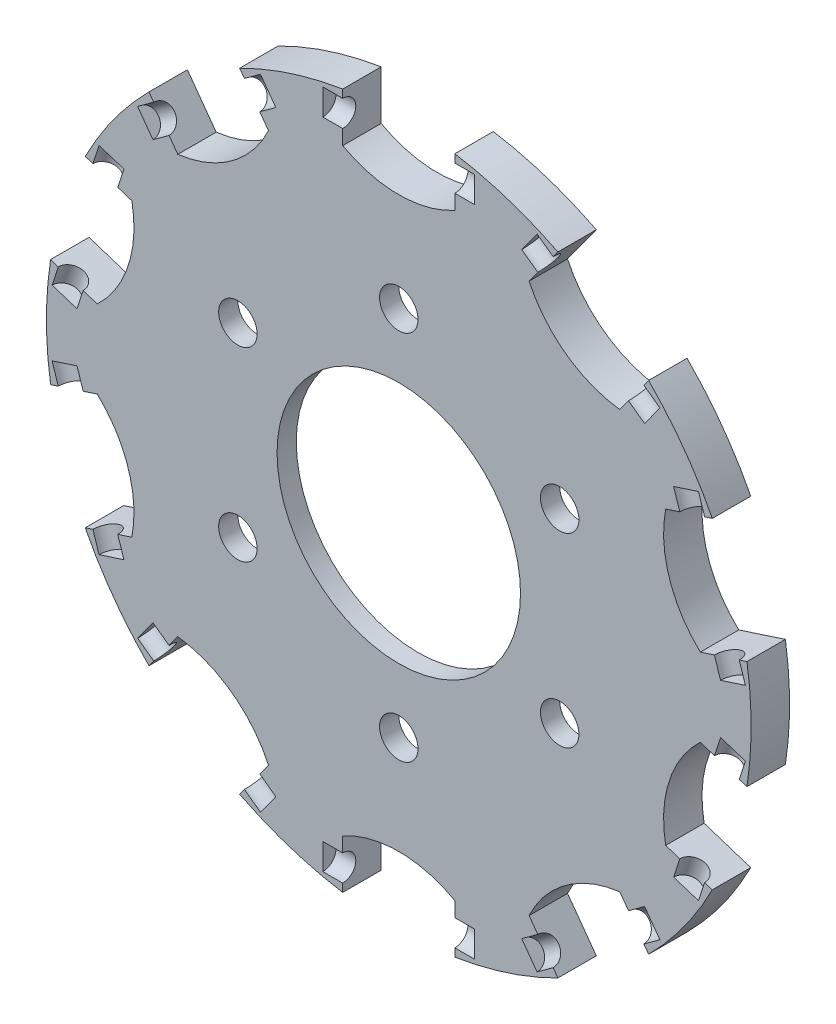
SolidWorks part; units mm, degrees
ref_plane "Front Plane" through (0, 0, 0) normal (0, 0, 1) x (1, 0, 0)
ref_plane "Top Plane" through (0, 0, 0) normal (0, 1, 0) x (1, 0, 0)
ref_plane "Right Plane" through (0, 0, 0) normal (1, 0, 0) x (0, 0, -1)
sketch "Sketch2" plane through (0, 0, 0) normal (0, 0, 1) x (1, 0, 0)
  line L2 (-4.375, 27.1498) -> (-4.375, 23.324)
  line L3 (4.375, 27.1498) -> (4.375, 23.324)
  line L4 (19.4977, 19.3931) -> (17.249, 16.298)
  line L5 (12.4188, 24.5362) -> (10.1701, 21.4411)
  line L6 (27.1729, 4.2289) -> (23.5344, 3.0466)
  line L7 (24.469, 12.5506) -> (20.8305, 11.3684)
  line L8 (24.469, -12.5506) -> (20.8305, -11.3684)
  line L9 (27.1729, -4.2289) -> (23.5344, -3.0466)
  line L10 (12.4188, -24.5362) -> (10.1701, -21.4411)
  line L11 (19.4977, -19.3931) -> (17.249, -16.298)
  line L12 (-4.375, -27.1498) -> (-4.375, -23.324)
  line L13 (4.375, -27.1498) -> (4.375, -23.324)
  line L14 (-19.4977, -19.3931) -> (-17.249, -16.298)
  line L15 (-12.4188, -24.5362) -> (-10.1701, -21.4411)
  line L16 (-27.1729, -4.2289) -> (-23.5344, -3.0466)
  line L17 (-24.469, -12.5506) -> (-20.8305, -11.3684)
  line L18 (-24.469, 12.5506) -> (-20.8305, 11.3684)
  line L19 (-27.1729, 4.2289) -> (-23.5344, 3.0466)
  line L20 (-12.4188, 24.5362) -> (-10.1701, 21.4411)
  line L21 (-19.4977, 19.3931) -> (-17.249, 16.298)
  circle A0 centre (0, 0) radius 27.5
  circle A1 centre (0, 0) radius 14.5 construction
  circle A2 centre (0, 0) radius 18.75 construction
  circle A3 centre (-12.5574, 7.25) radius 1.5
  circle A4 centre (0, 14.5) radius 1.5
  circle A5 centre (12.5574, 7.25) radius 1.5
  circle A6 centre (12.5574, -7.25) radius 1.5
  circle A7 centre (0, -14.5) radius 1.5
  circle A8 centre (-12.5574, -7.25) radius 1.5
  arc A9 (-4.375, 23.324) -> (4.375, 23.324) centre (0, 31.2162) ccw
  arc A10 (10.1701, 21.4411) -> (17.249, 16.298) centre (18.3484, 25.2544) ccw
  arc A11 (20.8305, 11.3684) -> (23.5344, 3.0466) centre (29.6883, 9.6463) ccw
  arc A12 (23.5344, -3.0466) -> (20.8305, -11.3684) centre (29.6883, -9.6463) ccw
  arc A13 (17.249, -16.298) -> (10.1701, -21.4411) centre (18.3484, -25.2544) ccw
  arc A14 (4.375, -23.324) -> (-4.375, -23.324) centre (0, -31.2162) ccw
  arc A15 (-10.1701, -21.4411) -> (-17.249, -16.298) centre (-18.3484, -25.2544) ccw
  arc A16 (-20.8305, -11.3684) -> (-23.5344, -3.0466) centre (-29.6883, -9.6463) ccw
  arc A17 (-23.5344, 3.0466) -> (-20.8305, 11.3684) centre (-29.6883, 9.6463) ccw
  arc A18 (-17.249, 16.298) -> (-10.1701, 21.4411) centre (-18.3484, 25.2544) ccw
  circle A19 centre (0, 0) radius 9.5
  circle A20 centre (0, 0) radius 18.75
  point P25 (0, 0)
  point P75 (0, 0)
  dimension "D1" = 55
  dimension "37" = 29
  dimension "D3" = 37.5
  dimension "D4" = 3
  dimension "D8" = 19
  dimension "D6" = 10
  dimension "D7" = 8.75
  dimension "D5" = 6
extrude "Boss-Extrude2" add sketch "Sketch2" along normal blind 3 contours A18 L21 A0 L18 A17 L19 L16 A16 L17 L14 A15 L15 L12 A14 L13 L10 A13 L11 L8 A12 L9 L6 A11 L7 L4 A10 L5 L3 A9 L2 L20 A8 A1 A3 A4 A5 A6 | A8 A1 A7 A6 A5 A4 A3 A19 region at (-5.1479, 25.2369, 0) region at (-18.2197, 0, 0)
extrude "Boss-Extrude3" add sketch "Sketch2<4>" along normal blind 3 contours A20 A8 A1 A3 A4 A5 A6 A7 region at (-18.2197, 0, 0)
sketch "Sketch2<4>" plane through (0, 0, 0) normal (0, 0, 1) x (1, 0, 0) same geometry as "Sketch2"
sketch "Sketch3" plane through (0, 0, 3) normal (0, 0, 1) x (1, 0, 0)
  line L0 (0, 28.1882) -> (0, 8.7236) construction
  line L1 (-4.375, 27.1498) -> (4.375, 27.1498) construction
  line L2 (4.375, 27.1498) -> (4.375, 23.324) construction
  line L3 (-6.683, 25.5) -> (6.8867, 25.5) construction
  line L4 (-5.925, 26.52) -> (5.925, 26.52)
  line L5 (5.925, 26.52) -> (5.925, 25.5)
  line L6 (-5.925, 26.52) -> (-5.925, 25.5)
  line L7 (5.925, 25.5) -> (-5.925, 25.5)
  arc A0 (12.4188, 24.5362) -> (4.375, 27.1498) centre (0, 0) ccw construction
  point P15 (0, 26.52)
  point P18 (0, 0)
  dimension "D1" = 25.5
  dimension "D2" = 11.85
  dimension "D3" = 1.02
  dimension "D4" = 1.02
revolve "Cut-Revolve1" cut sketch "Sketch3" angle 360 about L7
pattern_circular "CirPattern1" count 10 over 360 about axis through (0, 0, 0) along (0, 0, 1) of "Cut-Revolve1"
sketch "Sketch4" plane through (0, 0, 3) normal (0, 0, 1) x (1, 0, 0)
sketch "Sketch5" plane through (0, 0, 0) normal (0, 0, -1) x (-1, 0, 0)
  circle A0 centre (0, 0) radius 18.75
  dimension "D1" = 37.5
extrude "Cut-Extrude2" cut sketch "Sketch5" against normal blind 1.5
